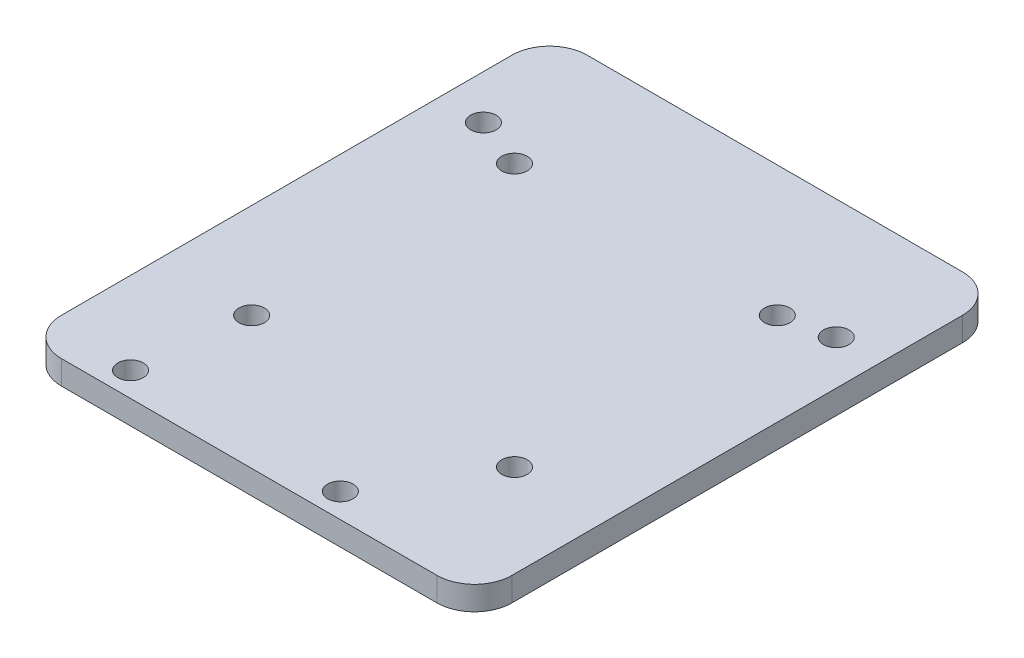
SolidWorks part; units mm, degrees
ref_plane "Front Plane" through (0, 0, 0) normal (0, 0, 1) x (1, 0, 0)
ref_plane "Top Plane" through (0, 0, 0) normal (0, 1, 0) x (1, 0, 0)
ref_plane "Right Plane" through (0, 0, 0) normal (1, 0, 0) x (0, 0, -1)
sketch "Sketch1" plane through (0, 0, 0) normal (0, 1, 0) x (1, 0, 0)
  line L1 (30, -35) -> (-30, -35)
  line L2 (30, -35) -> (30, 35)
  line L3 (30, 35) -> (-30, 35)
  line L4 (-30, -35) -> (-30, 35)
  line L5 (30, -35) -> (-30, 35) construction
  line L6 (30, 35) -> (-30, -35) construction
  point P0 (0, 0)
  dimension "D1" = 60
  dimension "D2" = 70
extrude "Boss-Extrude1" add sketch "Sketch1" along normal blind 3.175
hole_wizard "M3 Clearance Hole1" positions "Sketch3" profile "Sketch2" hole size "M3" standard "ANSI Metric" end condition through all
sketch "Sketch3" plane through (0, 3.175, 0) normal (0, 1, 0) x (1, 0, 0)
  point P0 (17.6754, 17.6517)
  point P3 (17.6754, -17.3483)
  point P6 (-17.3246, -17.3483)
  point P9 (-17.3246, 17.6517)
sketch "Sketch2" plane through (17.6754, 3.175, -17.6517) normal (1, 0, 0) x (0, 0, 1)
  line L0 (0, 0) -> (0, 3.175)
  line L1 (0, 3.175) -> (1.7, 3.175)
  line L2 (1.7, 3.175) -> (1.7, 0)
  line L5 (1.7, 0) -> (0, 0)
  line L11 (0, -6.35) -> (0, 107.95) construction
  dimension "Thru Hole Dia." = 3.4
  dimension "Thru Hole Depth" = 3.175
hole_wizard "M3 Clearance Hole2" positions "Sketch5" profile "Sketch4" hole size "M3" standard "ANSI Metric" end condition through all
sketch "Sketch5" plane through (0, 3.175, 0) normal (0, 1, 0) x (1, 0, 0)
  point P0 (-19.05, -31.75)
  point P3 (8.89, -31.75)
  point P6 (24.13, 19.05)
  point P9 (-24.13, 20.32)
sketch "Sketch4" plane through (-19.05, 3.175, 31.75) normal (1, 0, 0) x (0, 0, 1)
  line L0 (0, 0) -> (0, 3.175)
  line L1 (0, 3.175) -> (1.7, 3.175)
  line L2 (1.7, 3.175) -> (1.7, 0)
  line L5 (1.7, 0) -> (0, 0)
  line L11 (0, -6.35) -> (0, 107.95) construction
  dimension "Thru Hole Dia." = 3.4
  dimension "Thru Hole Depth" = 3.175
fillet "Fillet1" radius 5 4 edges at (-30, 1.5875, -35) (30, 1.5875, -35) (30, 1.5875, 35) (-30, 1.5875, 35)
